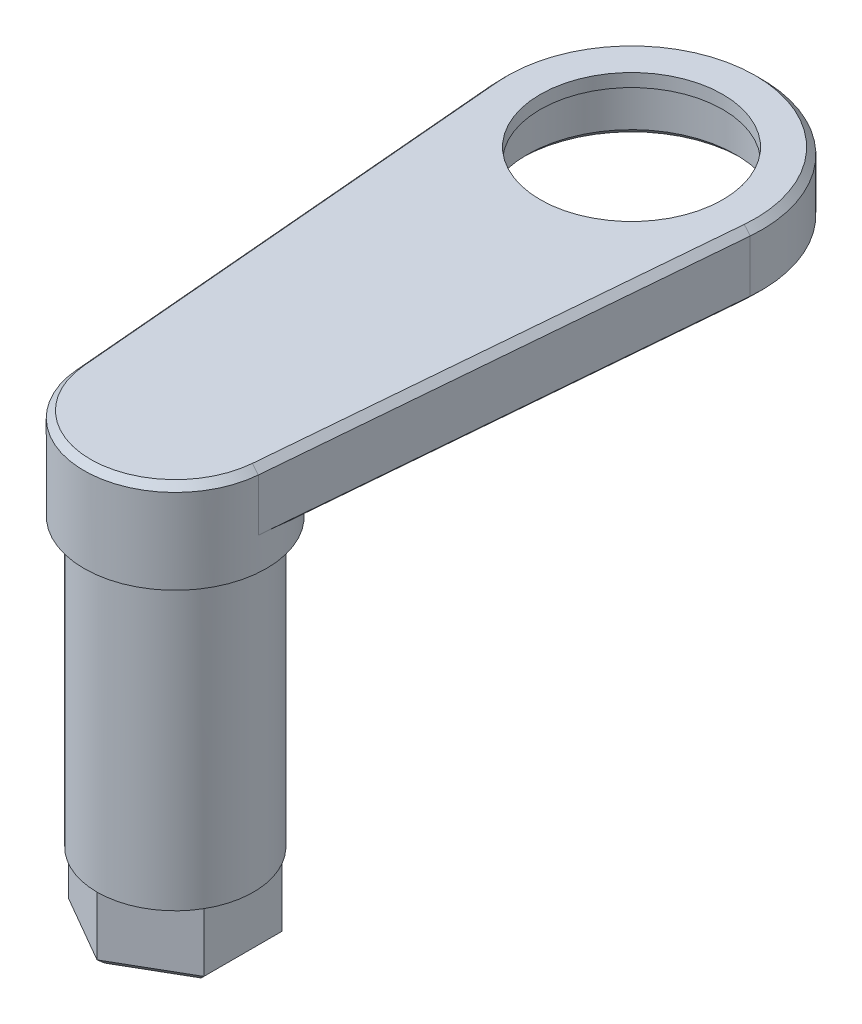
SolidWorks part; units mm, degrees
ref_plane "Front Plane" through (0, 0, 0) normal (0, 0, 1) x (1, 0, 0)
ref_plane "Top Plane" through (0, 0, 0) normal (0, 1, 0) x (1, 0, 0)
ref_plane "Right Plane" through (0, 0, 0) normal (1, 0, 0) x (0, 0, -1)
sketch "Sketch1" plane through (0, 0, 0) normal (0, 0, 1) x (1, 0, 0)
  line L0 (0, 0) -> (6, 0)
  line L2 (7, 24) -> (0, 24)
  line L3 (0, 24) -> (0, 0)
  line L4 (6, 0) -> (6, 22)
  line L5 (6, 22) -> (7, 22)
  line L6 (7, 22) -> (7, 24)
  point P7 (6.8303, 23.8825)
  point P9 (0, 0)
  point P10 (4.3933, 23.8825)
  point P11 (6.7206, 23.8825)
  dimension "D1" = 24
  dimension "D2" = 2
  dimension "D3" = 6
  dimension "D4" = 1
revolve "Revolve1" add sketch "Sketch1" angle 360 about L3
sketch "Sketch4" plane through (0, 0, 0) normal (0, -1, 0) x (1, 0, 0)
  line L1 (0, 6) -> (-5.1962, 3)
  line L2 (-5.1962, 3) -> (-5.1962, -3)
  line L3 (-5.1962, -3) -> (0, -6)
  line L4 (0, -6) -> (5.1962, -3)
  line L5 (5.1962, -3) -> (5.1962, 3)
  line L6 (5.1962, 3) -> (0, 6)
  circle A0 centre (0, 0) radius 5.1962 construction
  circle A1 centre (0, 0) radius 6 construction
  point P1 (-0.575, 5.9724)
  point P12 (0, 6)
  point P13 (0, 0)
  point P14 (0, 0)
extrude "Boss-Extrude3" add sketch "Sketch4" along normal blind 5
sketch "Sketch2" plane through (0, 24, 0) normal (0, 1, 0) x (1, 0, 0)
  line L0 (0, 0) -> (0, 35) construction
  line L1 (-6.9742, -0.6) -> (-9.9632, 34.1429)
  line L2 (6.9742, -0.6) -> (9.9632, 34.1429)
  circle A0 centre (0, 35) radius 8
  circle A1 centre (0, 0) radius 7
  arc A2 (-6.9742, -0.6) -> (6.9742, -0.6) centre (0, 0) ccw
  arc A3 (9.9632, 34.1429) -> (-9.9632, 34.1429) centre (0, 35) ccw
  circle A4 centre (0, 35) radius 10 construction
  dimension "D2" = 16
  dimension "D4" = 35
  dimension "D1" = 0
  dimension "D3" = 2
extrude "Boss-Extrude1" add sketch "Sketch2" along normal blind 5
sketch "Sketch3" plane through (0, 29, 0) normal (0, 1, 0) x (1, 0, 0)
  circle A0 centre (0, 35) radius 8 construction
  circle A1 centre (0, 35) radius 8
  circle A2 centre (0, 35) radius 7
  dimension "D1" = 1
extrude "Boss-Extrude2" add sketch "Sketch3" against normal blind 1
chamfer "Chamfer1" distance 0.5 angle 45 14 edges at (-8, 24, -35) (8.4687, 29, -16.7714) (0, 29, -45) (0, 29, 7) (-8.4687, 29, -16.7714) (8.4687, 24, -16.7714) (0, 24, -45) (-8.4687, 24, -16.7714) (5.1962, -5, 0) (2.5981, -5, -4.5) (-2.5981, -5, -4.5) (-5.1962, -5, 0) (-2.5981, -5, 4.5) (2.5981, -5, 4.5)
